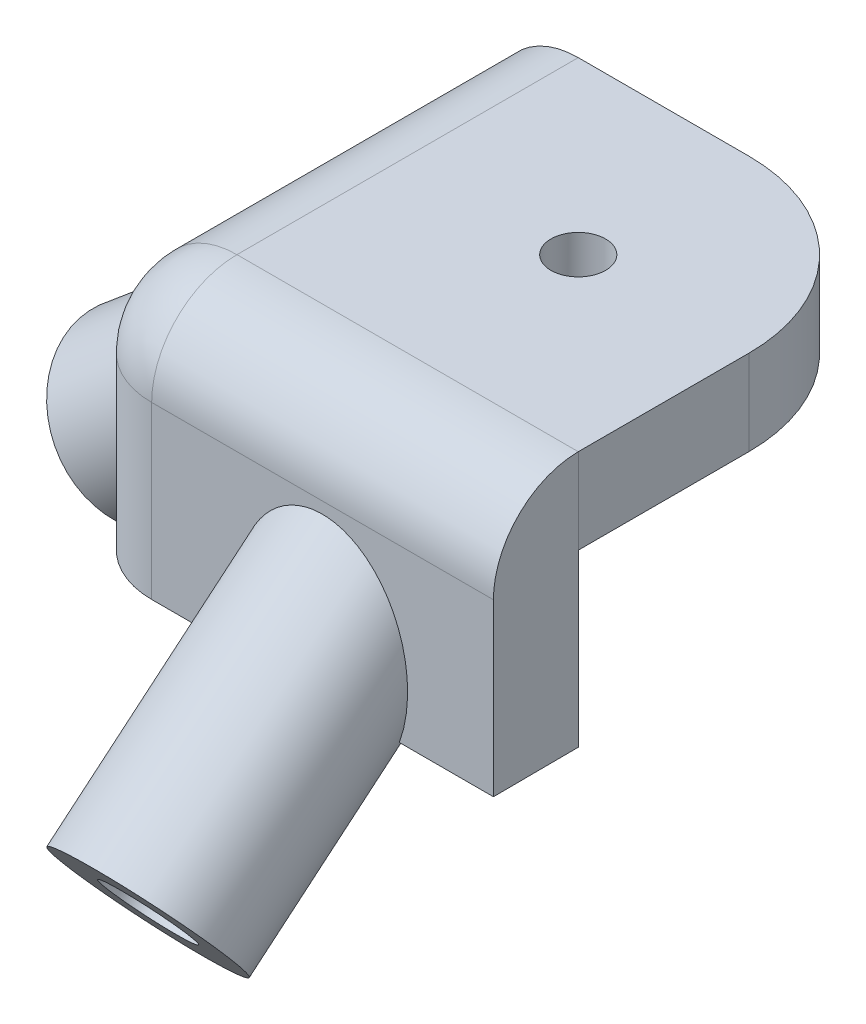
SolidWorks part; units mm, degrees
ref_plane "前基準面" through (0, 0, 0) normal (0, 0, 1) x (1, 0, 0)
ref_plane "上基準面" through (0, 0, 0) normal (0, 1, 0) x (1, 0, 0)
ref_plane "右基準面" through (0, 0, 0) normal (1, 0, 0) x (0, 0, -1)
sketch "草圖1" plane through (0, 0, 0) normal (0, 1, 0) x (1, 0, 0)
  line L1 (-10, -10) -> (10, -10)
  line L2 (-10, -10) -> (-10, 10)
  line L3 (-10, 10) -> (10, 10)
  line L4 (10, -10) -> (10, 10)
  line L5 (-10, -10) -> (10, 10) construction
  line L6 (-10, 10) -> (10, -10) construction
  point P0 (0, 0)
  dimension "D1" = 20
  dimension "D2" = 20
extrude "填料-伸長1" add sketch "草圖1" along normal blind 8
ref_plane "平面1" through (0, -1.6186, 1.929) normal (0, -0.6428, 0.766) x (1, 0, 0)
sketch "草圖2" plane through (0, -1.6186, 1.929) normal (0, -0.6428, 0.766) x (1, 0, 0)
  line L0 (-10, 6.4279) -> (10, 6.4279) construction
  line L1 (-10, 6.4279) -> (10, 6.4279) construction
  circle A0 centre (0, 6.4279) radius 5
  dimension "D1" = 10
extrude "填料-伸長2" add sketch "草圖2" along normal blind 25
ref_plane "平面2" through (-1.929, -1.6186, 0) normal (-0.766, -0.6428, 0) x (0, 0, 1)
sketch "草圖3" plane through (-1.929, -1.6186, 0) normal (-0.766, -0.6428, 0) x (0, 0, 1)
  line L0 (-10, 6.4279) -> (10, 6.4279) construction
  line L1 (-10, 6.4279) -> (10, 6.4279) construction
  circle A0 centre (0, 6.4279) radius 5
  dimension "D1" = 10
extrude "填料-伸長3" add sketch "草圖3" along normal blind 25
sketch "草圖4" plane through (0, 8, 0) normal (0, 1, 0) x (1, 0, 0)
  line L0 (0, 10) -> (10, 10)
  line L1 (10, 10) -> (10, 0)
  circle A0 centre (0, 0) radius 1.6
  arc A1 (10, 0) -> (0, 10) centre (0, 0) ccw
  dimension "D1" = 3.2
  dimension "D2" = 20
extrude "除料-伸長1" cut sketch "草圖4" against normal through all
sketch "草圖5" plane through (0, 0, 0) normal (0, -1, 0) x (1, 0, 0)
  line L0 (0, -10) -> (-10, -10) construction
  line L1 (10, 10) -> (10, 0) construction
  line L2 (0, -10) -> (-10, -10)
  line L3 (10, 10) -> (10, 0)
  line L4 (10, 10) -> (-10, 10)
  line L5 (-10, 10) -> (-10, -10)
  arc A0 (0, -10) -> (10, 0) centre (0, 0) ccw construction
  arc A1 (0, -10) -> (10, 0) centre (0, 0) ccw
sketch "草圖7" plane through (0, 0, 0) normal (0, -1, 0) x (1, 0, 0)
  line L0 (0, -10) -> (-10, -10) construction
  line L3 (4.3431, 4.3431) -> (-4.3431, 4.3431)
  line L4 (-4.3431, -4.3431) -> (-4.3431, 4.3431)
  line L7 (10, 10) -> (10, 0) construction
  line L8 (0, -10) -> (-4.3431, -10)
  line L9 (10, 4.3431) -> (10, 0)
  line L10 (4.3431, 4.3431) -> (10, 4.3431)
  line L11 (-4.3431, -4.3431) -> (-4.3431, -10)
  arc A0 (0, -10) -> (10, 0) centre (0, 0) ccw construction
  arc A1 (0, -10) -> (10, 0) centre (0, 0) ccw
  point P1 (0, 0)
sketch "草圖9" plane through (0, 8, 0) normal (0, 1, 0) x (1, 0, 0)
  line L0 (-10, 10) -> (-15, 10)
  line L1 (-15, 10) -> (-15, -15)
  line L2 (-15, -15) -> (10.0286, -15)
  line L3 (10.0286, -15) -> (10, -10)
  line L4 (10, -10) -> (-10, -10)
  line L5 (-10, -10) -> (-10, 10)
  dimension "D1" = 5
  dimension "D2" = 5
extrude "填料-伸長4" add sketch "草圖9" against normal blind 15
sketch "草圖10" plane through (0, -7, 0) normal (0, -1, 0) x (1, 0, 0)
  line L0 (10, 0) -> (10, 10)
  line L1 (10, 10) -> (-10, 10)
  line L2 (-10, 10) -> (-10, -10)
  line L3 (-10, -10) -> (0, -10)
  arc A0 (0, -10) -> (10, 0) centre (0, 0) ccw construction
  arc A1 (0, -10) -> (10, 0) centre (0, 0) ccw
extrude "除料-伸長5" cut sketch "草圖10" against normal blind 10
sketch "草圖11" plane through (-21.0801, -17.6883, 0) normal (-0.766, -0.6428, 0) x (0, 0, 1)
  circle A0 centre (0, 6.4279) radius 5 construction
  circle A1 centre (0, 6.4279) radius 5 construction
  circle A2 centre (0, 6.4279) radius 2.5
  dimension "D1" = 5
extrude "除料-伸長6" cut sketch "草圖11" against normal blind 10
sketch "草圖12" plane through (0, -17.6883, 21.0801) normal (0, -0.6428, 0.766) x (1, 0, 0)
  circle A0 centre (0, 6.4279) radius 5 construction
  circle A1 centre (0, 6.4279) radius 5 construction
  circle A2 centre (0, 6.4279) radius 2.5
  dimension "D1" = 5
extrude "除料-伸長7" cut sketch "草圖12" against normal blind 10
fillet "圓角3" radius 5 3 edges at (-2.4857, 8, 15) (-15, 8, 2.5) (-15, 0.5, 15)
